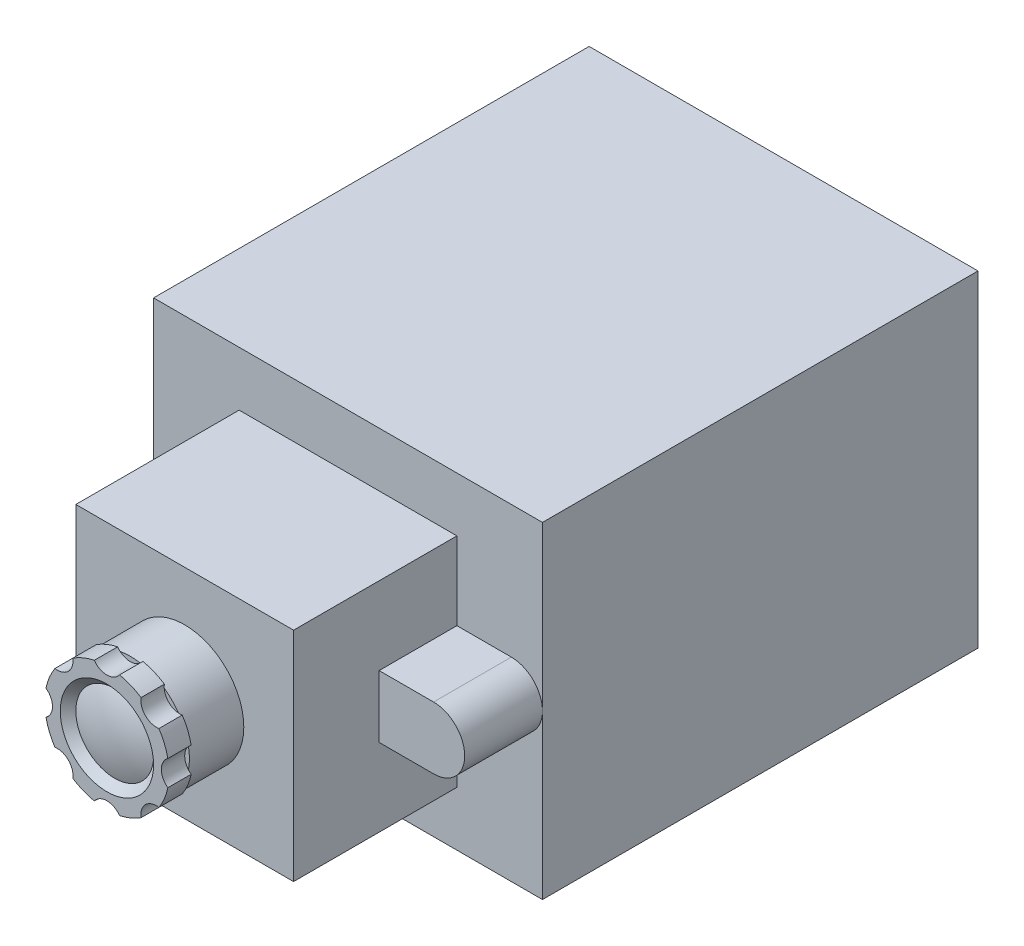
SolidWorks part; units mm, degrees
material "ABS"
ref_plane "前基準面" through (0, 0, 0) normal (0, 0, 1) x (1, 0, 0)
ref_plane "上基準面" through (0, 0, 0) normal (0, 1, 0) x (1, 0, 0)
ref_plane "右基準面" through (0, 0, 0) normal (1, 0, 0) x (0, 0, -1)
sketch "草圖1" plane through (0, 0, 0) normal (0, 0, 1) x (1, 0, 0)
  line L1 (-7, -7) -> (7, -7)
  line L2 (-7, -7) -> (-7, 7)
  line L3 (-7, 7) -> (7, 7)
  line L4 (7, -7) -> (7, 7)
  line L5 (-7, -7) -> (7, 7) construction
  line L6 (-7, 7) -> (7, -7) construction
  point P0 (0, 0)
  dimension "D1" = 14
extrude "填料-伸長1" add sketch "草圖1" along normal blind 10.5
sketch "草圖2" plane through (0, 0, 10.5) normal (0, 0, 1) x (1, 0, 0)
  circle A0 centre (0, 0) radius 3.8
  dimension "D1" = 7.6
extrude "填料-伸長2" add sketch "草圖2" along normal blind 5
sketch "草圖3" plane through (0, 0, 15.5) normal (0, 0, 1) x (1, 0, 0)
  circle A0 centre (0, 0) radius 4
  dimension "D1" = 8
extrude "填料-伸長3" add sketch "草圖3" against normal blind 1.5
sketch "草圖4" plane through (0, 0, 15.5) normal (0, 0, 1) x (1, 0, 0)
  line L0 (0, 0) -> (0, 4.5) construction
  circle A0 centre (0, 4.5) radius 1
  dimension "D1" = 2
  dimension "D2" = 4.5
extrude "除料-伸長2" cut sketch "草圖4" against normal up to surface (1.5 mm away) up to face at (3.8, 0, 14)
pattern_circular "環狀複製排列1" count 8 over 360 about axis through (0, 0, 15.5) along (0, 0, 1) of "除料-伸長2"
sketch "草圖5" plane through (0, 0, 0) normal (0, 0, -1) x (-1, 0, 0)
  line L1 (-12.5, -10.5) -> (12.5, -10.5)
  line L2 (-12.5, -10.5) -> (-12.5, 10.5)
  line L3 (-12.5, 10.5) -> (12.5, 10.5)
  line L4 (12.5, -10.5) -> (12.5, 10.5)
  line L5 (-12.5, -10.5) -> (12.5, 10.5) construction
  line L6 (-12.5, 10.5) -> (12.5, -10.5) construction
  point P0 (0, 0)
  dimension "D1" = 25
  dimension "D2" = 21
extrude "填料-伸長4" add sketch "草圖5" along normal blind 28
sketch "草圖6" plane through (0, 0, 0) normal (0, 0, 1) x (1, 0, 0)
  line L0 (-7, -2) -> (-7, 2)
  line L1 (-7, 7) -> (-7, -7) construction
  line L2 (-7, 2) -> (-10.5, 2)
  line L3 (-10.5, -2) -> (-7, -2)
  line L4 (-7, 7) -> (-7, -7) construction
  line L5 (-12.5, -10.5) -> (-12.5, 10.5) construction
  arc A0 (-10.5, -2) -> (-10.5, 2) centre (-10.5, 0) cw
  point P5 (-7, 0)
  point P8 (-6.0341, 0)
  point P9 (-7, -2)
  dimension "D1" = 2
extrude "填料-伸長5" add sketch "草圖6" along normal blind 5
mirror "鏡射1" about plane through (0, 0, 0) normal (1, 0, 0) of "填料-伸長5"
sketch "草圖9" plane through (0, 0, 15.5) normal (0, 0, 1) x (1, 0, 0)
  circle A0 centre (0, 0) radius 3
  dimension "D1" = 6
extrude "除料-伸長3" cut sketch "草圖9" against normal blind 0.5
chamfer "導角1" distance 0.5 1 edges at (3, 0, 15)
sketch "草圖10" plane through (0, 0, 0) normal (0, 1, 0) x (1, 0, 0)
  line L0 (0, 0) -> (0, -15.5)
  line L1 (3, -15.5) -> (2.5, -15) construction
  line L2 (-3, -15.5) -> (3, -15.5) construction
  line L3 (-2.5, -15) -> (2.5, -15)
  arc A0 (-2.5, -15) -> (2.5, -15) centre (0, -9) ccw
  point P11 (0, -15)
revolve "旋轉2" add sketch "草圖10" angle 360 about L0 region at (-0.9425, 0, 15.2007)
